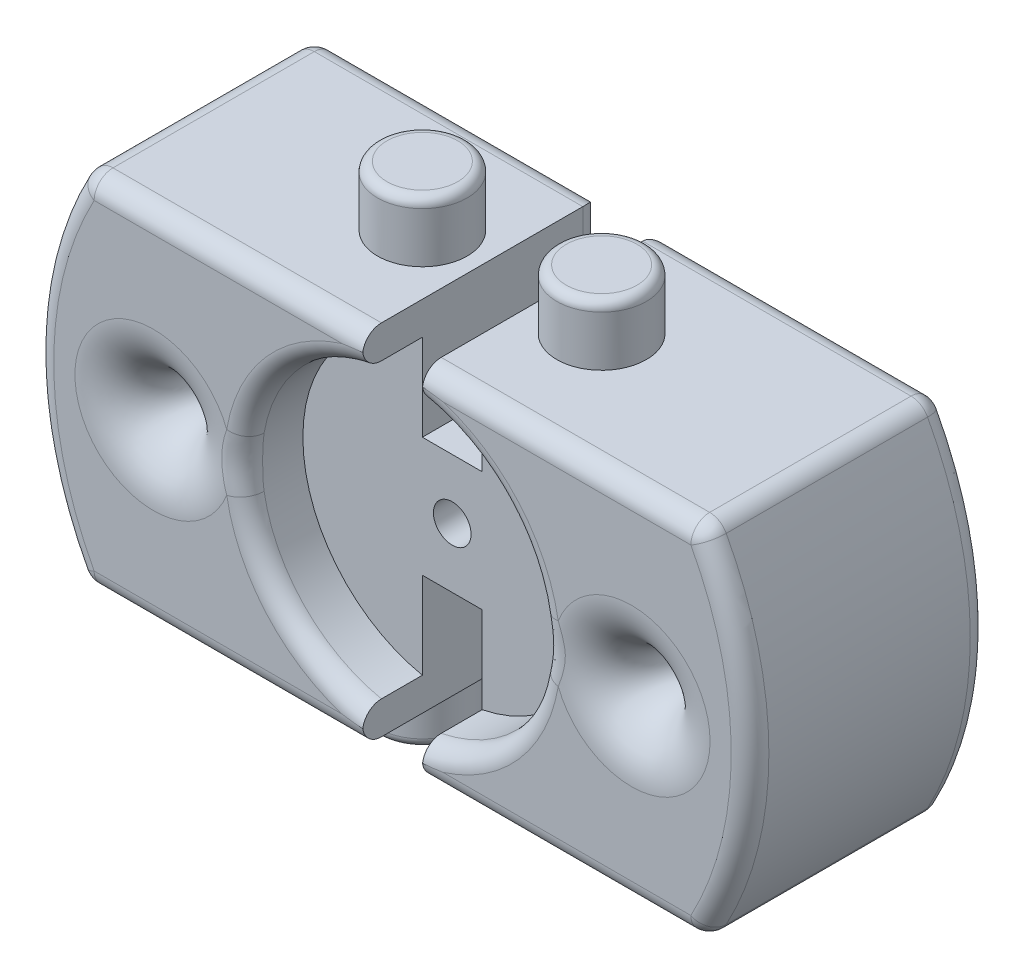
SolidWorks part; units mm, degrees
ref_plane "Front Plane" through (0, 0, 0) normal (0, 0, 1) x (1, 0, 0)
ref_plane "Top Plane" through (0, 0, 0) normal (0, 1, 0) x (1, 0, 0)
ref_plane "Right Plane" through (0, 0, 0) normal (1, 0, 0) x (0, 0, -1)
sketch "Sketch1" plane through (0, 0, 0) normal (0, 0, 1) x (1, 0, 0)
  line L0 (-0.7937, 4.7625) -> (-0.7937, 1.5875)
  line L1 (-0.7937, 1.5875) -> (0.7938, 1.5875)
  line L2 (0, 15.875) -> (0, 0) construction
  line L3 (0, 0) -> (6.35, 0) construction
  line L4 (0.7938, 4.7625) -> (0.7938, 1.5875)
  line L5 (0.7938, -4.7625) -> (0.7938, -1.5875)
  line L6 (-0.7937, -1.5875) -> (0.7938, -1.5875)
  line L7 (-0.7937, -4.7625) -> (-0.7937, -1.5875)
  line L8 (-0.7937, 4.7625) -> (-9.5, 4.7625)
  line L9 (-9.5, 4.7625) -> (-9.5, -4.7625)
  line L10 (-9.5, -4.7625) -> (-0.7937, -4.7625)
  line L12 (9.5, -4.7625) -> (0.7938, -4.7625)
  line L13 (9.5, 4.7625) -> (9.5, -4.7625)
  line L14 (0.7938, 4.7625) -> (9.5, 4.7625)
  circle A2 centre (0, 0) radius 0.5
  circle A3 centre (6.35, 0) radius 0.5
  circle A4 centre (-6.35, 0) radius 0.5
  point P9 (0, 1.5875)
  point P10 (0, -1.5875)
  dimension "D1" = 3.175
  dimension "D4" = 1
  dimension "D2" = 3.175
  dimension "D3" = 1.5875
  dimension "D5" = 6.35
  dimension "D6" = 19
extrude "Boss-Extrude1" add sketch "Sketch1" along normal blind 6.35
sketch "Sketch2" plane through (0, 0, 6.35) normal (0, 0, 1) x (1, 0, 0)
  circle A0 centre (0, 0) radius 3.9688
  dimension "D1" = 7.9375
extrude "Cut-Extrude2" cut sketch "Sketch2" against normal blind 1.5875
sketch "Sketch4" plane through (0, 4.7625, 0) normal (0, 1, 0) x (1, 0, 0)
  line L0 (0, 0) -> (0, -6.35) construction
  line L1 (0.7938, 0) -> (-0.7937, 0) construction
  line L3 (0, -3.175) -> (-2.3813, -3.175) construction
  line L4 (-0.7937, -6.35) -> (-9.5, -6.35) construction
  circle A0 centre (-2.3813, -3.175) radius 1.1906
  circle A1 centre (2.3813, -3.175) radius 1.1906
  dimension "D1" = 2.3813
  dimension "D2" = 2.3813
extrude "Boss-Extrude2" add sketch "Sketch4" along normal blind 1.5875
sketch "Sketch5" plane through (0, -4.7625, 0) normal (0, -1, 0) x (1, 0, 0)
  line L0 (-9.5, 3.175) -> (-2.3812, 3.175) construction
  line L1 (-9.5, 6.35) -> (-9.5, 0) construction
  line L2 (-2.3812, 3.175) -> (2.3813, 3.175) construction
  line L3 (2.3813, 3.175) -> (9.5, 3.175) construction
  line L4 (9.5, 6.35) -> (9.5, 0) construction
  circle A2 centre (-2.3812, 3.175) radius 1.1906
  circle A3 centre (2.3813, 3.175) radius 1.1906
  dimension "D2" = 2.3812
  dimension "D1" = 4.7625
extrude "Boss-Extrude3" add sketch "Sketch5" along normal blind 1.5875
fillet "Fillet4" radius 0.25 4 edges at (-2.3813, 6.35, 4.3656) (2.3813, 6.35, 1.9844) (2.3813, -6.35, 1.9844) (-2.3812, -6.35, 1.9844)
sketch "Sketch6" plane through (0, 0, 6.35) normal (0, 0, 1) x (1, 0, 0)
  line L1 (-12.3665, 10.9585) -> (14.0921, 10.9585)
  line L2 (-12.3665, 10.9585) -> (-12.3665, -9.5887)
  line L3 (-12.3665, -9.5887) -> (14.0921, -9.5887)
  line L4 (14.0921, 10.9585) -> (14.0921, -9.5887)
  circle A0 centre (0, 0) radius 9.5
  dimension "D1" = 19
extrude "Cut-Extrude4" cut sketch "Sketch6" against normal through all
fillet "Fillet6" radius 0.5 4 edges at (8.22, -4.7625, 3.175) (-8.22, -4.7625, 3.175) (-8.22, 4.7625, 3.175) (8.22, 4.7625, 3.175)
fillet "Fillet2" radius 1.5875 4 edges at (-6.85, 0, 0) (-6.85, 0, 6.35) (6.85, 0, 0) (6.85, 0, 6.35)
fillet "Fillet7" radius 0.5 29 edges at (8.1831, 4.6917, 0) (4.3602, 4.7625, 0) (0.7938, 3.175, 0) (0, 1.5875, 0) (-0.7937, 3.175, 0) (-4.3602, 4.7625, 0) (-8.1831, 4.6917, 0) (-9.5, 0, 0) (-8.1831, -4.6917, 0) (-4.3602, -4.7625, 0) (-0.7937, -3.175, 0) (0, -1.5875, 0) (0.7938, -3.175, 0) (4.3602, -4.7625, 0) (8.1831, -4.6917, 0) (9.5, 0, 0) (0.5, 0, 0) (3.9688, 0, 6.35) (4.3602, 4.7625, 6.35) (8.1831, 4.6917, 6.35) (9.5, 0, 6.35) (8.1831, -4.6917, 6.35) (4.3602, -4.7625, 6.35) (-8.1831, 4.6917, 6.35) (-4.3602, 4.7625, 6.35) (-3.9688, 0, 6.35) (-4.3602, -4.7625, 6.35) (-8.1831, -4.6917, 6.35) (-9.5, 0, 6.35)
